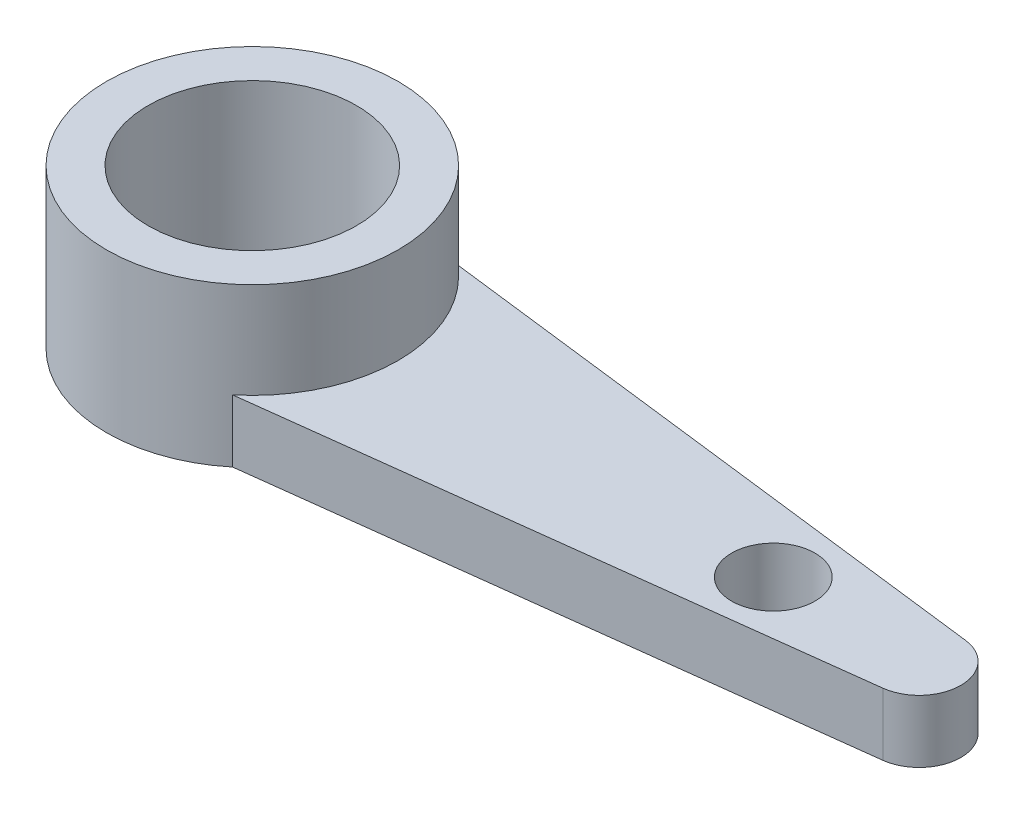
SolidWorks part; units mm, degrees
ref_plane "Front Plane" through (0, 0, 0) normal (0, 0, 1) x (1, 0, 0)
ref_plane "Top Plane" through (0, 0, 0) normal (0, 1, 0) x (1, 0, 0)
ref_plane "Right Plane" through (0, 0, 0) normal (1, 0, 0) x (0, 0, -1)
sketch "Sketch1" plane through (0, 0, 0) normal (0, 1, 0) x (1, 0, 0)
  line L0 (-2.2271, 2.7) -> (-16.122, 0.9925)
  line L1 (-2.2271, -2.7) -> (-16.122, -0.9925)
  line L2 (0, 0) -> (0, 7.2501) construction
  line L3 (2.2271, -2.7) -> (16.122, -0.9925)
  line L4 (2.2271, 2.7) -> (16.122, 0.9925)
  circle A0 centre (0, 0) radius 2.5
  circle A1 centre (0, 0) radius 3.5
  circle A2 centre (-16, 0) radius 1
  circle A3 centre (16, 0) radius 1
  circle A4 centre (-12.5, 0) radius 1
  circle A5 centre (12.5, 0) radius 1
  dimension "D1" = 5
  dimension "D2" = 7
  dimension "D3" = 2
  dimension "D4" = 2
  dimension "D8" = 12.5
  dimension "D9" = 2
  dimension "D5" = 32
  dimension "D6" = 16
  dimension "D7" = 5.4
extrude "Boss-Extrude1" add sketch "Sketch1" along normal blind 1.5 contours A0 A1 | A3 L4 A1 L3 A5 | A3 L1 region at (0, 0, -3.401) region at (8.0587, 0, 0) region at (16, 0, 0)
extrude "Boss-Extrude2" add sketch "Sketch1<3>" along normal blind 3.8 contours A0 A1 region at (0, 0, -3.401)
sketch "Sketch1<3>" plane through (0, 0, 0) normal (0, 1, 0) x (1, 0, 0) same geometry as "Sketch1"
